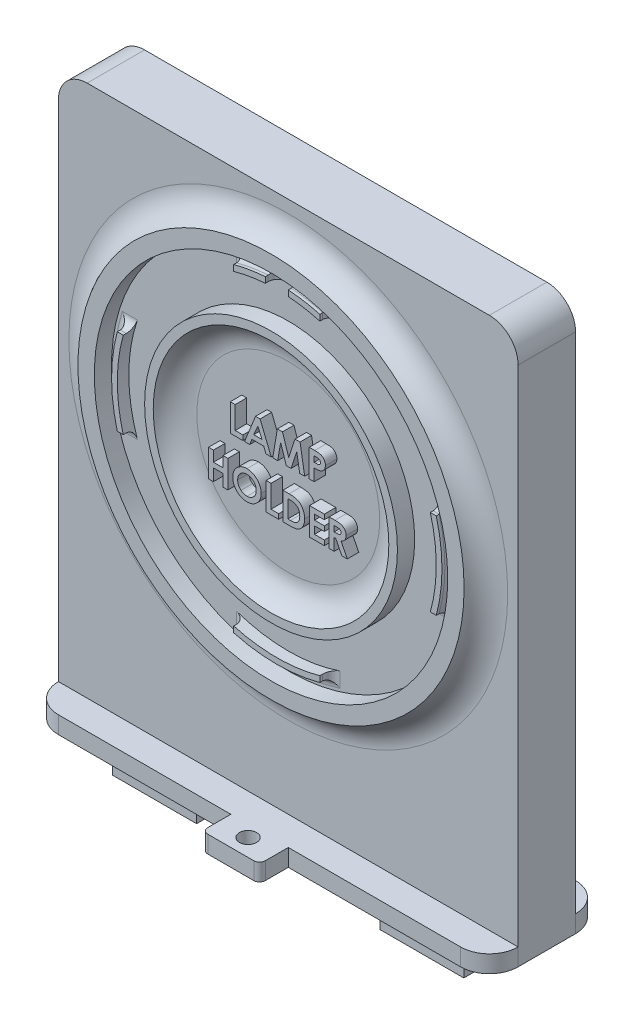
SolidWorks part; units mm, degrees
ref_plane "Front Plane" through (0, 0, 0) normal (0, 0, 1) x (1, 0, 0)
ref_plane "Top Plane" through (0, 0, 0) normal (0, 1, 0) x (1, 0, 0)
ref_plane "Right Plane" through (0, 0, 0) normal (1, 0, 0) x (0, 0, -1)
sketch "Sketch1" plane through (0, 0, 0) normal (0, 0, 1) x (1, 0, 0)
  line L1 (-40, 55.35) -> (40, 55.35)
  line L2 (-40, 55.35) -> (-40, -55.35)
  line L3 (-40, -55.35) -> (40, -55.35)
  line L4 (40, 55.35) -> (40, -55.35)
  line L5 (-40, 55.35) -> (40, -55.35) construction
  line L6 (-40, -55.35) -> (40, 55.35) construction
  point P0 (0, 0)
  dimension "D1" = 80
  dimension "D2" = 110.7
extrude "Boss-Extrude1" add sketch "Sketch1" along normal blind 10
sketch "Sketch3" plane through (0, 0, 0) normal (0, 0, -1) x (-1, 0, 0)
  line L0 (0, -55.35) -> (0, -45) construction
  line L1 (40, -55.35) -> (-40, -55.35) construction
  line L2 (-40, 55.35) -> (40, 55.35) construction
  line L8 (20.95, -57.2) -> (25.55, -57.2) construction
  line L9 (-20.95, -59.05) -> (-15.95, -59.05)
  line L10 (-30.55, -59.05) -> (-25.55, -59.05)
  line L11 (-30.55, -59.05) -> (-30.55, -61.75)
  line L12 (-30.55, -61.75) -> (-15.95, -61.75)
  line L13 (-15.95, -59.05) -> (-15.95, -61.75)
  line L14 (-30.55, -59.05) -> (-15.95, -61.75) construction
  line L15 (-30.55, -61.75) -> (-15.95, -59.05) construction
  line L16 (-25.55, -55.35) -> (-20.95, -55.35)
  line L17 (-25.55, -55.35) -> (-25.55, -59.05)
  line L19 (-20.95, -55.35) -> (-20.95, -59.05)
  line L20 (-25.55, -55.35) -> (-20.95, -59.05) construction
  line L21 (-25.55, -59.05) -> (-20.95, -55.35) construction
  line L22 (30.55, -59.05) -> (30.55, -61.75)
  line L23 (30.55, -61.75) -> (15.95, -61.75)
  line L24 (15.95, -59.05) -> (15.95, -61.75)
  line L25 (20.95, -59.05) -> (15.95, -59.05)
  line L26 (20.95, -55.35) -> (20.95, -59.05)
  line L27 (25.55, -55.35) -> (20.95, -55.35)
  line L28 (25.55, -55.35) -> (25.55, -59.05)
  line L29 (30.55, -59.05) -> (25.55, -59.05)
  point P5 (0, -50.175)
  point P12 (-23.25, -60.4)
  point P17 (-23.25, -57.2)
  point P32 (-40, -55.35)
  dimension "D1" = 110.7
  dimension "D2" = 16.75
  dimension "D3" = 2.7
  dimension "D4" = 14.6
  dimension "D5" = 4.6
  dimension "D6" = 3.7
extrude "Boss-Extrude2" add sketch "Sketch3" against normal blind 10
sketch "Sketch11" plane through (0, 0, 10) normal (0, 0, 1) x (1, 0, 0)
  line L19 (40, -55.35) -> (40, 55.35) construction
  line L28 (-40, 55.35) -> (40, 55.35)
  line L29 (-40, 55.35) -> (-40, 40.35)
  line L30 (-40, 40.35) -> (40, 40.35)
  line L31 (40, 55.35) -> (40, 40.35)
  dimension "D1" = 15
extrude "Cut-Extrude1" cut sketch "Sketch11" against normal blind 10 contours L29 L28 L31 L30
sketch "Sketch4" plane through (0, -55.35, 0) normal (0, -1, 0) x (1, 0, 0)
  line L0 (0, 10) -> (0, 0) construction
  line L1 (-20.95, 10) -> (20.95, 10) construction
  line L2 (5, -5) -> (35, -5)
  line L3 (-40, 10) -> (40, 10)
  line L4 (-40, 10) -> (-40, 0)
  line L5 (-40, 0) -> (40, 0)
  line L6 (40, 10) -> (40, 0)
  line L7 (-40, 10) -> (40, 0) construction
  line L8 (-40, 0) -> (40, 10) construction
  line L9 (-35, 15) -> (-5, 15)
  line L10 (-40, 10) -> (-40, 0)
  line L11 (-35, -5) -> (-5, -5)
  line L12 (40, 10) -> (40, 0)
  line L13 (-40, 15) -> (40, -5) construction
  line L14 (-40, -5) -> (40, 15) construction
  line L16 (-5, -5) -> (-5, -9)
  line L17 (-4, -10) -> (4, -10)
  line L18 (5, -5) -> (5, -9)
  line L20 (-40, 5) -> (40, 5) construction
  line L21 (-5, 15) -> (-5, 19)
  line L22 (5, 15) -> (5, 19)
  line L23 (-4, 20) -> (4, 20)
  line L24 (5, 15) -> (35, 15)
  arc A0 (35, 15) -> (40, 10) centre (35, 10) cw
  arc A1 (35, -5) -> (40, 0) centre (35, 0) ccw
  arc A2 (-40, 0) -> (-35, -5) centre (-35, 0) ccw
  arc A3 (-35, 15) -> (-40, 10) centre (-35, 10) ccw
  circle A4 centre (0, -7) radius 1.5
  arc A5 (-5, -9) -> (-4, -10) centre (-4, -9) ccw
  arc A6 (4, -10) -> (5, -9) centre (4, -9) ccw
  circle A7 centre (0, 17) radius 1.5
  arc A8 (-5, 19) -> (-4, 20) centre (-4, 19) cw
  arc A9 (4, 20) -> (5, 19) centre (4, 19) cw
  point P5 (0, 5)
  point P11 (0, 5)
  point P37 (-5, -10)
  line M5 (20.95, 10) -> (-20.95, 10)
  line M7 (-20.95, 0) -> (20.95, 0)
  dimension "D3" = 5
  dimension "D6" = 3
  dimension "D7" = 1
  dimension "D1" = 20
  dimension "D2" = 80
  dimension "D4" = 5
  dimension "D5" = 10
  dimension "D8" = 3
extrude "Boss-Extrude3" add sketch "Sketch4" against normal blind 3 contours A9 L23 A8 L21 L9 A3 L3 A0 L24 L22 A7 M5 | L17 A6 L18 L2 A1 L5 A2 L11 L16 A5 A4 M7 region at (0, -55.35, -2.9637) region at (0, -55.35, 12.9637)
sketch "Sketch5" plane through (0, 0, 10) normal (0, 0, 1) x (1, 0, 0)
  circle A0 centre (0, 0) radius 33.6
  circle A1 centre (0, 0) radius 30.75
  dimension "D1" = 61.5
  dimension "D2" = 67.2
extrude "Boss-Extrude4" add sketch "Sketch5" along normal blind 3
sketch "Sketch12" plane through (0, 0, 10) normal (0, 0, 1) x (1, 0, 0)
  line L0 (0, 28.75) -> (0, 27.75) construction
  line L1 (-7.5, 29) -> (7.5, 29)
  line L2 (-7.5, 29) -> (-7.5, -29)
  line L3 (-7.5, -29) -> (7.5, -29)
  line L4 (7.5, 29) -> (7.5, -29)
  line L5 (-7.5, 29) -> (7.5, -29) construction
  line L6 (-7.5, -29) -> (7.5, 29) construction
  line L7 (-29, 7.5) -> (29, 7.5)
  line L8 (-29, 7.5) -> (-29, -7.5)
  line L9 (-29, -7.5) -> (29, -7.5)
  line L10 (29, 7.5) -> (29, -7.5)
  line L11 (-29, 7.5) -> (29, -7.5) construction
  line L12 (-29, -7.5) -> (29, 7.5) construction
  line L14 (-2, 28.8222) -> (2, 28.8222)
  line L15 (-2, 28.8222) -> (-2, 27.6778)
  line L16 (-2, 27.6778) -> (2, 27.6778)
  line L17 (2, 28.8222) -> (2, 27.6778)
  line L18 (-2, 28.8222) -> (2, 27.6778) construction
  line L19 (-2, 27.6778) -> (2, 28.8222) construction
  circle A0 centre (0, 0) radius 27.75
  circle A1 centre (0, 0) radius 28.75
  point P14 (0, 28.25)
  dimension "D1" = 55.5
  dimension "D2" = 57.5
  dimension "D3" = 15
  dimension "D4" = 58
  dimension "D5" = 15
  dimension "D6" = 58
  dimension "D7" = 4
extrude "Boss-Extrude5" add sketch "Sketch12" along normal blind 2 contours L15 A1 L2 A0 | L4 A1 L17 A0 | L7 A1 L9 A0 | L9 A1 L7 A0 | L2 A1 L4 A0 region at (-4.7656, 27.7983, 10) region at (4.7656, 27.7983, 10) region at (-27.9111, 0, 10) region at (27.9111, 0, 10) region at (0, -27.9111, 10)
sketch "Sketch13" plane through (0, 0, 10) normal (0, 0, 1) x (1, 0, 0)
  circle A0 centre (0, 0) radius 22
  circle A1 centre (0, 0) radius 20.5
  dimension "D1" = 41
  dimension "D2" = 44
extrude "Boss-Extrude6" add sketch "Sketch13" along normal blind 3
fillet "Fillet1" radius 5 2 edges at (20.5, 0, 10) (33.6, 0, 10)
fillet "Fillet2" radius 1.5 15 edges at (27.2359, -7.5, 10) (28.75, 0, 10) (27.2359, 7.5, 10) (7.5, 27.2359, 10) (4.7725, 28.3511, 10) (2, 28.1791, 10) (-2, 28.1791, 10) (-4.7725, 28.3511, 10) (-7.5, 27.2359, 10) (-27.2359, 7.5, 10) (-28.75, 0, 10) (-27.2359, -7.5, 10) (7.5, -27.2359, 10) (0, -28.75, 10) (-7.5, -27.2359, 10)
fillet "Fillet3" radius 5 2 edges at (40, 40.35, 5) (-40, 40.35, 5)
sketch "Sketch14" plane through (0, 0, 10) normal (0, 0, 1) x (1, 0, 0)
  line L0 (15.7884, 2.0222) -> (-15.7884, 2.0222) construction
  circle A2 centre (0, 0) radius 15.9174 construction
  text T0 "<b>LAMP</b>\r\n<b>HOLDER</b>" font "Century Gothic" height in points 18
  point P1 (0, 0)
  point P9 (0, 0)
  point P11 (0, 0)
  point P15 (15.9174, 0)
extrude "Boss-Extrude7" add sketch "Sketch14" along normal blind 2
